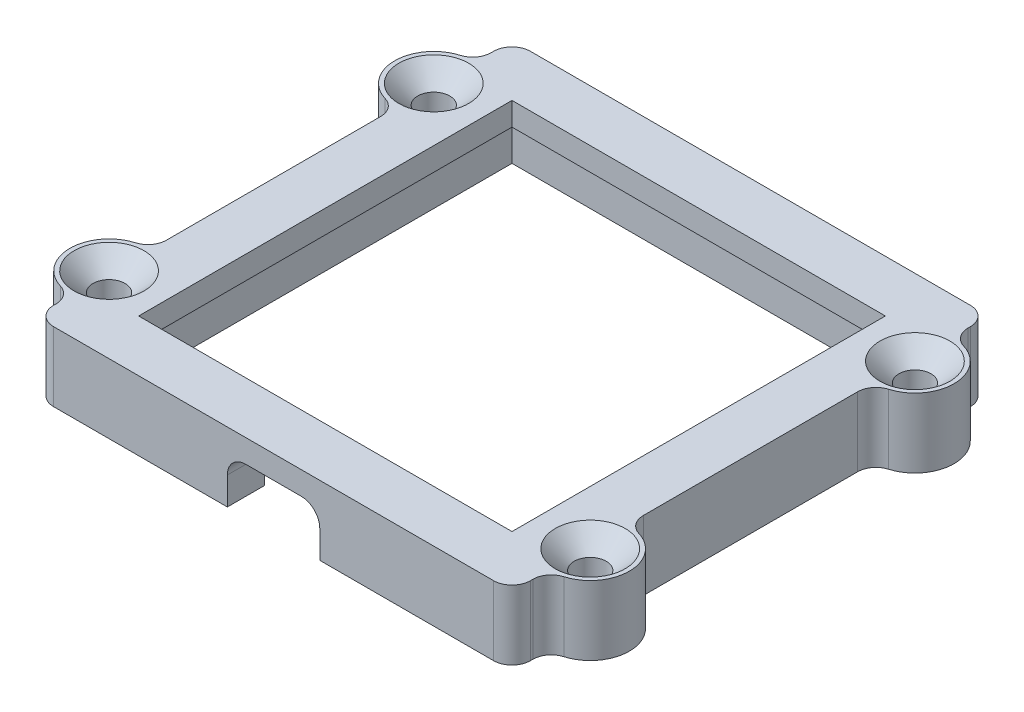
SolidWorks part; units mm, degrees
material "Custom Plastic"
ref_plane "Front Plane" through (0, 0, 0) normal (0, 0, 1) x (1, 0, 0)
ref_plane "Top Plane" through (0, 0, 0) normal (0, 1, 0) x (1, 0, 0)
ref_plane "Right Plane" through (0, 0, 0) normal (1, 0, 0) x (0, 0, -1)
sketch "Sketch1" plane through (0, 0, 0) normal (0, 1, 0) x (1, 0, 0)
  line L0 (-2.54, -2.54) -> (-2.54, 30.226)
  line L1 (0, 0) -> (27.686, 0)
  line L2 (0, 0) -> (0, 27.686)
  line L3 (0, 27.686) -> (27.686, 27.686)
  line L4 (27.686, 0) -> (27.686, 27.686)
  line L5 (-2.54, 30.226) -> (30.226, 30.226)
  line L6 (30.226, -2.54) -> (30.226, 30.226)
  line L7 (-2.54, -2.54) -> (30.226, -2.54)
  circle A0 centre (-2.6875, 24.9985) radius 1.1
  circle A1 centre (-2.6875, 2.6875) radius 1.1
  circle A2 centre (30.3735, 2.6875) radius 1.1
  circle A3 centre (30.3735, 24.9985) radius 1.1
  circle A4 centre (-2.6875, 24.9985) radius 2.6875
  circle A5 centre (-2.6875, 2.6875) radius 2.6875
  circle A6 centre (30.3735, 24.9985) radius 2.6875
  circle A7 centre (30.3735, 2.6875) radius 2.6875
  point P25 (-2.54, 22.6062)
  point P26 (36.5252, 5.6308)
  dimension "D4" = 2.2
  dimension "D5" = 2.2
  dimension "D6" = 2.2
  dimension "D7" = 2.2
  dimension "D1" = 2.54
  dimension "D2" = 27.686
  dimension "D3" = 27.686
  dimension "D8" = 1.5875
extrude "Boss-Extrude1" add sketch "Sketch1" along normal blind 3.175 contours L0 A4 A0 | A6 L6 L5 L0 A4 L2 L3 L4 | L0 A4 A0 | L0 A5 A1 | L0 A5 A1 | A5 L2 A4 L0 | A7 L4 L1 L2 A5 L0 L7 L6 | A7 L6 A6 L4 | L6 A7 A2 | L6 A7 A2 | L6 A6 A3 | L6 A6 A3
sketch "Sketch2" plane through (0, 3.175, 0) normal (0, 1, 0) x (1, 0, 0)
  line L0 (1.016, 26.67) -> (26.67, 1.016) construction
  line L1 (1.016, 26.67) -> (26.67, 26.67)
  line L2 (1.016, 26.67) -> (1.016, 1.016)
  line L3 (1.016, 1.016) -> (26.67, 1.016)
  line L4 (26.67, 26.67) -> (26.67, 1.016)
  line L5 (27.686, 27.686) -> (0, 0) construction
  line L10 (27.686, 0) -> (27.686, 27.686)
  line L11 (0, 0) -> (27.686, 0)
  line L12 (0, 27.686) -> (0, 0)
  line L13 (27.686, 27.686) -> (0, 27.686)
  line L14 (30.226, 5.3709) -> (30.226, 22.3151)
  line L15 (30.226, 27.6819) -> (30.226, 30.226)
  line L16 (30.226, 30.226) -> (-2.54, 30.226)
  line L17 (-2.54, 30.226) -> (-2.54, 27.6819)
  line L18 (-2.54, 22.3151) -> (-2.54, 5.3709)
  line L19 (-2.54, 0.0041) -> (-2.54, -2.54)
  line L20 (-2.54, -2.54) -> (30.226, -2.54)
  line L21 (30.226, -2.54) -> (30.226, 0.0041)
  line L22 (30.226, 5.3709) -> (30.226, 22.3151)
  line L23 (30.226, 27.6819) -> (30.226, 30.226)
  line L24 (30.226, 30.226) -> (-2.54, 30.226)
  line L25 (-2.54, 30.226) -> (-2.54, 27.6819)
  line L26 (-2.54, 22.3151) -> (-2.54, 5.3709)
  line L27 (-2.54, 0.0041) -> (-2.54, -2.54)
  line L28 (-2.54, -2.54) -> (30.226, -2.54)
  line L29 (30.226, -2.54) -> (30.226, 0.0041)
  line L30 (27.686, 0) -> (27.686, 27.686)
  line L31 (0, 0) -> (27.686, 0)
  line L32 (0, 27.686) -> (0, 0)
  line L33 (27.686, 27.686) -> (0, 27.686)
  circle A1 centre (30.3735, 2.6875) radius 1.1
  circle A2 centre (30.3735, 2.6875) radius 1.1
  circle A3 centre (-2.6875, 2.6875) radius 1.1
  arc A4 (30.226, 0.0041) -> (30.226, 5.3709) centre (30.3735, 2.6875) ccw
  arc A5 (30.226, 22.3151) -> (30.226, 27.6819) centre (30.3735, 24.9985) ccw
  arc A6 (-2.54, 27.6819) -> (-2.54, 22.3151) centre (-2.6875, 24.9985) ccw
  arc A7 (-2.54, 5.3709) -> (-2.54, 0.0041) centre (-2.6875, 2.6875) ccw
  arc A8 (30.226, 0.0041) -> (30.226, 5.3709) centre (30.3735, 2.6875) ccw
  arc A9 (30.226, 22.3151) -> (30.226, 27.6819) centre (30.3735, 24.9985) ccw
  arc A10 (-2.54, 27.6819) -> (-2.54, 22.3151) centre (-2.6875, 24.9985) ccw
  arc A11 (-2.54, 5.3709) -> (-2.54, 0.0041) centre (-2.6875, 2.6875) ccw
  circle A12 centre (-2.6875, 2.6875) radius 1.1
  circle A13 centre (30.3735, 24.9985) radius 1.1
  circle A14 centre (30.3735, 24.9985) radius 1.1
  circle A15 centre (-2.6875, 24.9985) radius 1.1
  circle A16 centre (-2.6875, 24.9985) radius 1.1
  point P4 (-0.3443, 0)
  point P8 (13.843, 13.843)
  point P9 (13.843, 13.843)
  point P10 (13.716, 13.716)
  point P23 (24.6961, 24.7445)
  point P26 (27.1333, 27.432)
  arc M24 (30.226, 0.0041) -> (30.226, 5.3709) centre (30.3735, 2.6875) ccw
  line M25 (30.226, 5.3709) -> (30.226, 22.3151)
  arc M26 (30.226, 22.3151) -> (30.226, 27.6819) centre (30.3735, 24.9985) ccw
  line M27 (30.226, 27.6819) -> (30.226, 30.226)
  line M28 (30.226, 30.226) -> (-2.54, 30.226)
  line M29 (-2.54, 30.226) -> (-2.54, 27.6819)
  arc M30 (-2.54, 27.6819) -> (-2.54, 22.3151) centre (-2.6875, 24.9985) ccw
  line M31 (-2.54, 22.3151) -> (-2.54, 5.3709)
  arc M32 (-2.54, 5.3709) -> (-2.54, 0.0041) centre (-2.6875, 2.6875) ccw
  line M33 (-2.54, 0.0041) -> (-2.54, -2.54)
  line M34 (-2.54, -2.54) -> (30.226, -2.54)
  line M35 (30.226, -2.54) -> (30.226, 0.0041)
  line M36 (27.686, 27.686) -> (27.686, 0)
  line M37 (27.686, 0) -> (0, 0)
  line M38 (0, 0) -> (0, 27.686)
  line M39 (0, 27.686) -> (27.686, 27.686)
  circle M40 centre (30.3735, 2.6875) radius 1.1
  circle M41 centre (-2.6875, 2.6875) radius 1.1
  circle M42 centre (30.3735, 24.9985) radius 1.1
  circle M43 centre (-2.6875, 24.9985) radius 1.1
  dimension "D1" = 25.654
  dimension "D2" = 25.654
  dimension "D3" = 0
  dimension "D4" = 0
  dimension "D5" = 0
  dimension "D6" = 0
  dimension "D7" = 0
  dimension "D8" = 0
extrude "Boss-Extrude2" add sketch "Sketch2" along normal blind 1.5875 contours M35 M24 M25 M26 M27 M28 M29 M30 M31 M32 M33 M34 M39 M36 M37 M38 M40 M42 M43 M41 | L1 L4 L3 L2 M36 M39 M38 M37
chamfer "Chamfer1" distance 1.3 angle 45 4 edges at (30.3735, 4.7625, -23.8985) (30.3735, 4.7625, -1.5875) (-2.6875, 4.7625, -1.5875) (-2.6875, 4.7625, -23.8985)
fillet "Fillet1" radius 1.27 12 edges at (30.226, 2.3812, -0.0041) (30.226, 2.3812, 2.54) (-2.54, 2.3812, 2.54) (-2.54, 2.3812, -0.0041) (-2.54, 2.3812, -5.3709) (-2.54, 2.3812, -22.3151) (-2.54, 2.3812, -27.6819) (-2.54, 2.3812, -30.226) (30.226, 2.3812, -30.226) (30.226, 2.3812, -27.6819) (30.226, 2.3812, -22.3151) (30.226, 2.3812, -5.3709)
sketch "Sketch3" plane through (0, 0, 2.54) normal (0, 0, 1) x (1, 0, 0)
  line L0 (-1.27, 0) -> (28.956, 0) construction
  line L1 (10.668, 0) -> (17.018, 0)
  line L2 (10.668, 0) -> (10.668, 3.175)
  line L3 (10.668, 3.175) -> (17.018, 3.175)
  line L4 (17.018, 0) -> (17.018, 3.175)
  line L5 (0, 3.175) -> (27.686, 3.175) construction
  line L6 (0, 3.175) -> (27.686, 3.175)
  point P6 (13.843, 0)
  point P7 (13.716, 0)
  point P10 (16.891, 3.175)
  line M2 (-1.27, 0) -> (28.956, 0)
  dimension "D1" = 6.35
extrude "Cut-Extrude1" cut sketch "Sketch3" against normal up to next and the other way through all contours L4 L3 L2 M2
fillet "Fillet2" radius 1.27 2 edges at (10.668, 3.175, 1.27) (17.018, 3.175, 1.27)
